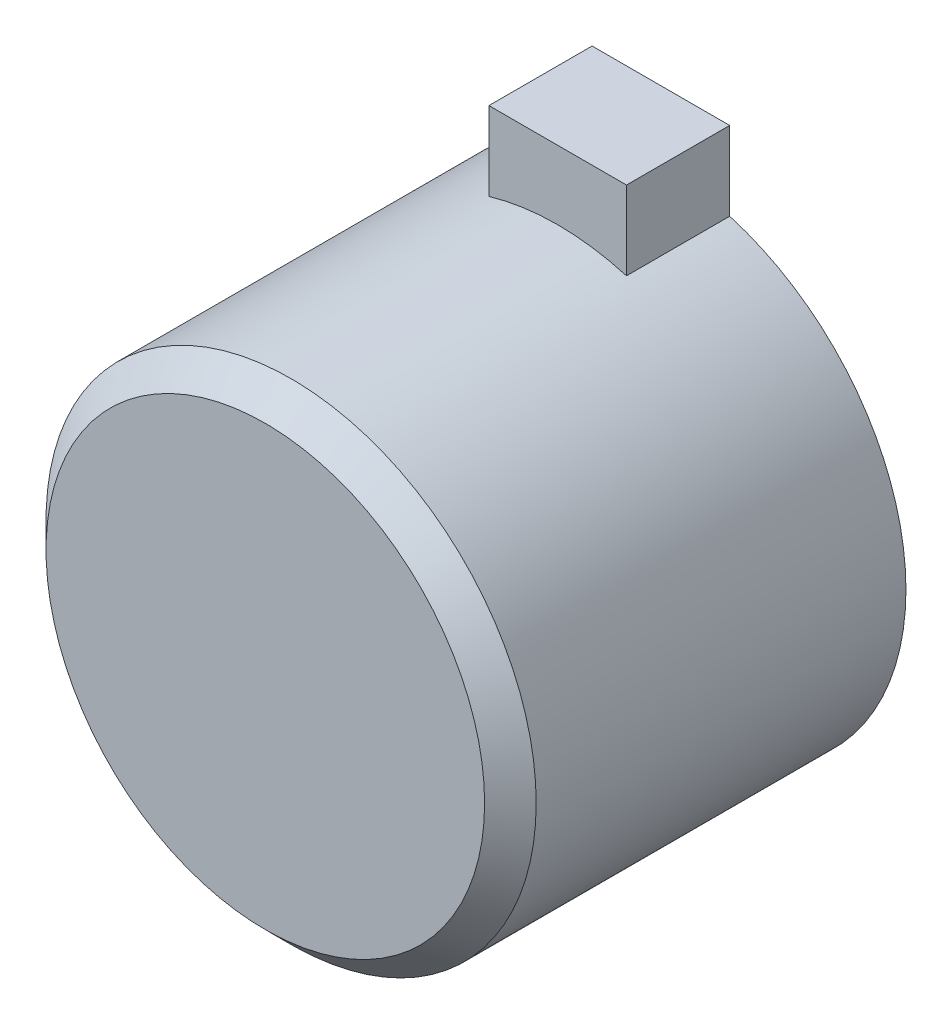
SolidWorks part; units mm, degrees
ref_plane "Front Plane" through (0, 0, 0) normal (0, 0, 1) x (1, 0, 0)
ref_plane "Top Plane" through (0, 0, 0) normal (0, 1, 0) x (1, 0, 0)
ref_plane "Right Plane" through (0, 0, 0) normal (1, 0, 0) x (0, 0, -1)
sketch "SK_Body" plane through (0, 0, 0) normal (0, 1, 0) x (1, 0, 0)
  line L0 (0, -10) -> (0, 56) construction
  line L1 (0, 0) -> (25.5, 0)
  line L2 (25.5, 0) -> (28.5, 3)
  line L3 (28.5, 3) -> (28.5, 46)
  line L4 (28.5, 46) -> (25.5, 46)
  line L5 (25.5, 46) -> (0, 46)
  line L6 (0, 46) -> (0, 0)
  dimension "P1" = 10
  dimension "P2" = 56
  dimension "R_front" = 25.5
  dimension "P4" = 28.5
  dimension "P5" = 3
  dimension "R_body" = 28.5
  dimension "L_body" = 46
  dimension "P8" = 25.5
  dimension "P9" = 46
  dimension "P10" = 46
revolve "Housing_Body" add sketch "SK_Body" angle 360 about L0
ref_plane "PL_Rear" through (0, 0, -46) normal (0, 0, 1) x (1, 0, 0)
sketch "SK_RearHole" plane through (0, 0, -46) normal (0, 0, 1) x (1, 0, 0)
  circle A0 centre (23, 0) radius 1.25
  dimension "D_rh" = 2.5
  dimension "R_rh" = 23
extrude "Rear_Tapped_Hole" cut sketch "SK_RearHole" along normal blind 8
ref_axis "AX_Joint" through (0, 0, -48.3) along (0, 0, 1)
pattern_circular "Rear_Hole_Pattern" count 4 over 360 about axis through (0, 0, -48.3) along (0, 0, 1) of "Rear_Tapped_Hole"
sketch "SK_Connector" plane through (0, 0, -46) normal (0, 0, 1) x (1, 0, 0)
  line L0 (-8, 24.5) -> (8, 24.5)
  line L1 (8, 24.5) -> (8, 36.5)
  line L2 (8, 36.5) -> (-8, 36.5)
  line L3 (-8, 36.5) -> (-8, 24.5)
  dimension "P1" = 8
  dimension "P2" = 24.5
  dimension "P3" = 8
  dimension "P4" = 24.5
  dimension "P5" = 8
  dimension "P6" = 36.5
  dimension "P7" = 8
  dimension "P8" = 36.5
extrude "Connector_Zone" add sketch "SK_Connector" along normal blind 12
equation "\"D_act\" = 57"
equation "\"L_housing\" = 46"
equation "\"PCD_rear\" = 46"
equation "\"D_rear_hole\" = 2.5"
equation "\"D_bearing_boss\" = 36"
equation "\"R_front@SK_Body\" = \"D_act\"/2-3.0"
equation "\"R_body@SK_Body\" = \"D_act\"/2"
equation "\"L_body@SK_Body\" = \"L_housing\""
equation "\"D_rh@SK_RearHole\" = \"D_rear_hole\""
equation "\"R_rh@SK_RearHole\" = \"PCD_rear\"/2"
